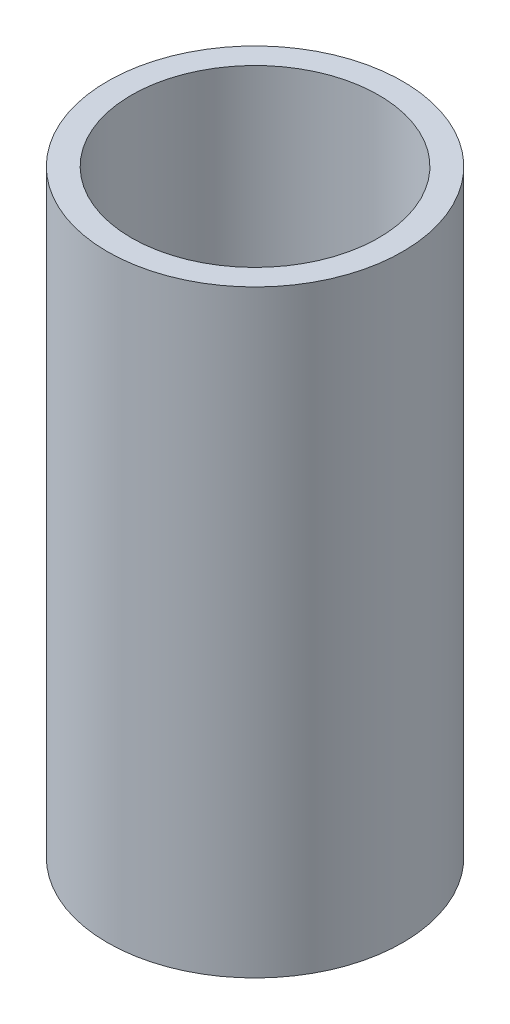
SolidWorks part; units mm, degrees
ref_plane "Front Plane" through (0, 0, 0) normal (0, 0, 1) x (1, 0, 0)
ref_plane "Top Plane" through (0, 0, 0) normal (0, 1, 0) x (1, 0, 0)
ref_plane "Right Plane" through (0, 0, 0) normal (1, 0, 0) x (0, 0, -1)
sketch "Sketch1" plane through (0, 0, 0) normal (0, 1, 0) x (1, 0, 0)
  circle A0 centre (0, 0) radius 3.1
  circle A1 centre (0, 0) radius 3.7
  dimension "D1" = 7.4
  dimension "D2" = 6.2
extrude "Boss-Extrude1" add sketch "Sketch1" along normal blind 15
